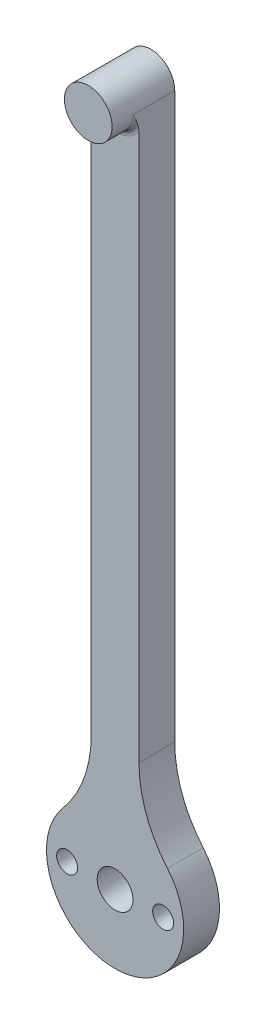
SolidWorks part; units mm, degrees
ref_plane "Plan de face" through (0, 0, 0) normal (0, 0, 1) x (1, 0, 0)
ref_plane "Plan de dessus" through (0, 0, 0) normal (0, 1, 0) x (1, 0, 0)
ref_plane "Plan de droite" through (0, 0, 0) normal (1, 0, 0) x (0, 0, -1)
sketch "Esquisse1" plane through (0, 0, 0) normal (0, 0, 1) x (1, 0, 0)
  line L0 (-4, 0) -> (-4, -104.2181)
  line L1 (4, 0) -> (4, -104.2181)
  arc A0 (4, 0) -> (-4, 0) centre (0, 0) ccw
  arc A1 (-4, -104.2181) -> (4, -104.2181) centre (0, -115) ccw
  dimension "D1" = 8
  dimension "D2" = 115
  dimension "D3" = 23
extrude "Boss.-Extru.1" add sketch "Esquisse1" along normal blind 6
sketch "Esquisse2" plane through (0, 0, 0) normal (0, 0, 1) x (1, 0, 0)
  line L0 (0, -55) -> (0, 55) construction
  circle A0 centre (0, -115) radius 10.5
  arc A1 (-4, -104.2181) -> (4, -104.2181) centre (0, -115) ccw construction
  dimension "D1" = 21
extrude "Enlèv. mat.-Extru.3" cut sketch "Esquisse2" along normal blind 1.5
sketch "Esquisse3" plane through (0, 0, 0) normal (0, 0, 1) x (1, 0, 0)
  line L0 (0, -55) -> (0, 55) construction
  circle A0 centre (0, -115) radius 3
  arc A1 (-4, -104.2181) -> (4, -104.2181) centre (0, -115) ccw construction
  dimension "D1" = 6
extrude "Enlèv. mat.-Extru.5" cut sketch "Esquisse3" along normal through all
sketch "Esquisse4" plane through (0, 0, 6) normal (0, 0, 1) x (1, 0, 0)
  circle A0 centre (0, 0) radius 4
extrude "Boss.-Extru.2" add sketch "Esquisse4" along normal blind 4.5
fillet "Congé1" radius 20 2 edges at (4, -104.2181, 3) (-4, -104.2181, 3)
fillet "Congé2" radius 1 1 edges at (0, -4, 6)
sketch "Esquisse5" plane through (0, 0, 6) normal (0, 0, 1) x (1, 0, 0)
  circle A0 centre (-8.05, -115) radius 1.75
  circle A1 centre (8.05, -115) radius 1.75
  circle A2 centre (0, -115) radius 6.3 construction
  arc A3 (-8.7619, -107.5516) -> (8.7619, -107.5516) centre (0, -115) ccw construction
  dimension "D1" = 3.5
  dimension "D2" = 3.5
  dimension "D3" = 12.6
extrude "Enlèv. mat.-Extru.6" cut sketch "Esquisse5" against normal through all
